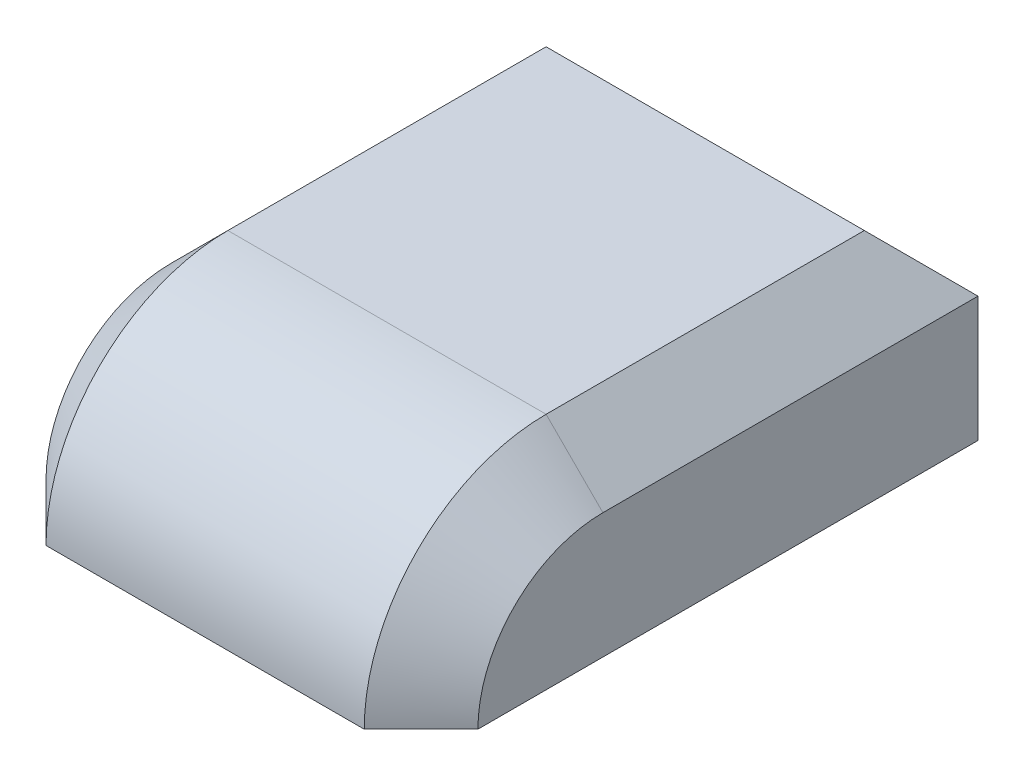
SolidWorks part; units mm, degrees
material "ABS PC"
ref_plane "Front Plane" through (0, 0, 0) normal (0, 0, 1) x (1, 0, 0)
ref_plane "Top Plane" through (0, 0, 0) normal (0, 1, 0) x (1, 0, 0)
ref_plane "Right Plane" through (0, 0, 0) normal (1, 0, 0) x (0, 0, -1)
sketch "Sketch1" plane through (0, 0, 0) normal (0, 1, 0) x (1, 0, 0)
  line L1 (-19, -24.5) -> (19, -24.5)
  line L2 (-19, -24.5) -> (-19, 24.5)
  line L3 (-19, 24.5) -> (19, 24.5)
  line L4 (19, -24.5) -> (19, 24.5)
  line L5 (-19, -24.5) -> (19, 24.5) construction
  line L6 (-19, 24.5) -> (19, -24.5) construction
  point P0 (0, 0)
  dimension "D1" = 49
  dimension "D2" = 38
extrude "Boss-Extrude1" add sketch "Sketch1" along normal blind 16
fillet "Fillet1" radius 16 1 edges at (0, 16, 24.5)
chamfer "Chamfer1" distance 5 angle 45 5 edges at (-19, 11.3137, 19.8137) (-19, 16, -8) (19, 11.3137, 19.8137) (19, 16, -8) (0, 16, -24.5)
